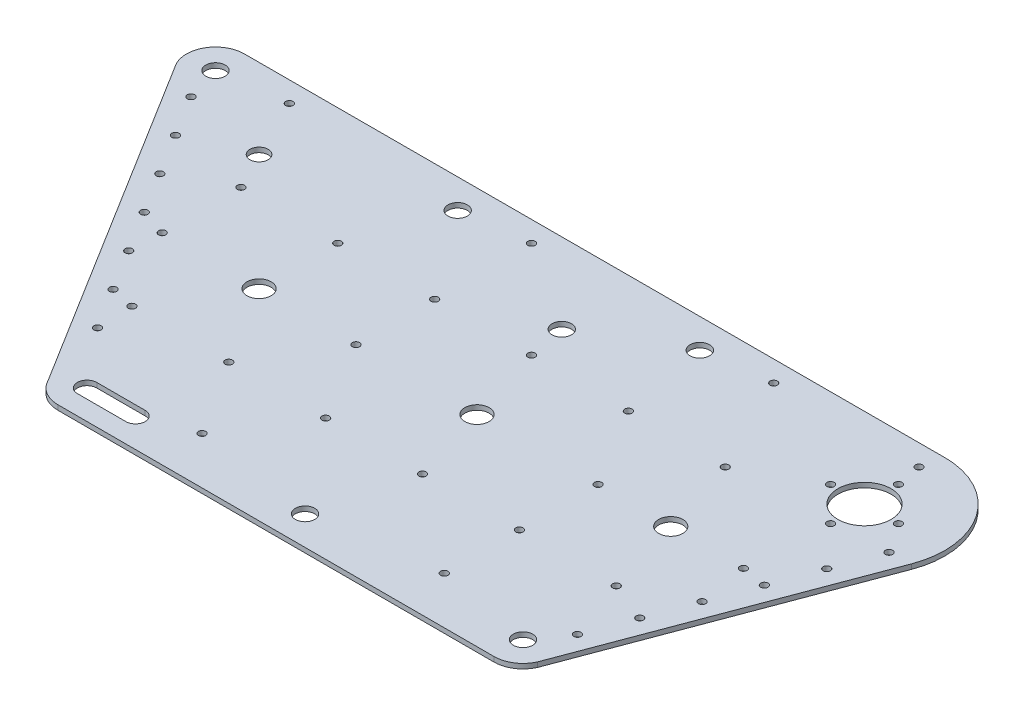
SolidWorks part; units mm, degrees
ref_plane "Front Plane" through (0, 0, 0) normal (0, 0, 1) x (1, 0, 0)
ref_plane "Top Plane" through (0, 0, 0) normal (0, 1, 0) x (1, 0, 0)
ref_plane "Right Plane" through (0, 0, 0) normal (1, 0, 0) x (0, 0, -1)
sketch "Sketch2" plane through (0, 0, 0) normal (0, 1, 0) x (1, 0, 0)
  line L0 (-106.005, 144.9436) -> (182.9628, 145.1972)
  line L1 (160.9924, -19) -> (-18.9986, -19)
  line L2 (171.9007, -12) -> (214.0696, 100.3323)
  line L3 (-18.9986, -3) -> (1.0004, -3)
  line L4 (1.0003, -11) -> (-18.9986, -11)
  line L5 (-29.6999, -12.4286) -> (-116.0853, 126.6112)
  circle A0 centre (182.992, 112) radius 11
  circle A1 centre (-18.9988, 64) radius 5
  circle A2 centre (70.9964, 64) radius 5
  circle A3 centre (150.9927, 64) radius 5
  ellipse E0 centre (-105.9945, 133) end of major axis (-105.9945, 137) minor radius 4
  ellipse E1 centre (160.9926, -7) end of major axis (160.9926, -3) minor radius 4
  ellipse E2 centre (-18.9986, -7) end of major axis (-18.9986, -11) minor radius 4 (-18.9986, -3) -> (-18.9986, -11) ccw
  ellipse E3 centre (182.992, 112) end of major axis (182.992, 123) minor radius 11
  ellipse E4 centre (-105.9945, 133) end of major axis (-105.9945, 144.9436) minor radius 11.943 (-106.005, 144.9436) -> (-116.0853, 126.6112) ccw
  ellipse E5 centre (182.992, 112) end of major axis (182.992, 145.1972) minor radius 33.1955 (214.0696, 100.3323) -> (182.9628, 145.1972) ccw
  ellipse E6 centre (1.0003, -7) end of major axis (1.0004, -3) minor radius 4 (1.0003, -11) -> (1.0004, -3) ccw
  ellipse E7 centre (182.9908, 126) end of major axis (182.9908, 127.5) minor radius 1.4999
  ellipse E8 centre (196.9901, 112) end of major axis (196.9901, 113.5) minor radius 1.4999
  ellipse E9 centre (168.9915, 112) end of major axis (168.9915, 113.5) minor radius 1.4999
  ellipse E10 centre (182.9908, 98) end of major axis (182.9908, 99.5) minor radius 1.4999
  ellipse E11 centre (-18.9986, -7) end of major axis (-18.9986, -19) minor radius 11.9993 (-29.6999, -12.4286) -> (-18.9986, -19) ccw
  ellipse E12 centre (160.9926, -7) end of major axis (160.9926, 5) minor radius 11.9994 (160.9924, -19) -> (171.9007, -12) ccw
  ellipse E13 centre (120.9939, 0.5) end of major axis (120.994, 2) minor radius 1.4999
  ellipse E14 centre (20.9989, 0.5) end of major axis (20.9989, 2) minor radius 1.4999
  ellipse E15 centre (120.9939, 64) end of major axis (120.994, 65.5) minor radius 1.4999
  ellipse E16 centre (20.9989, 64) end of major axis (20.9989, 65.5) minor radius 1.4999
  ellipse E17 centre (-58.997, 64) end of major axis (-58.997, 65.5) minor radius 1.4999
  ellipse E18 centre (180.9909, 64) end of major axis (180.9909, 65.5) minor radius 1.4999
  ellipse E19 centre (-78.996, 136.5) end of major axis (-78.996, 138) minor radius 1.4999
  ellipse E20 centre (20.9989, 136.5) end of major axis (20.9989, 138) minor radius 1.4999
  ellipse E21 centre (120.9939, 136.5) end of major axis (120.994, 138) minor radius 1.4999
  ellipse E22 centre (60.9969, 96.5) end of major axis (60.9969, 98) minor radius 1.4999
  ellipse E23 centre (140.9929, 96.5) end of major axis (140.9929, 98) minor radius 1.4999
  ellipse E24 centre (160.992, 31.5) end of major axis (160.992, 33) minor radius 1.4999
  ellipse E25 centre (80.996, 31.5) end of major axis (80.996, 33) minor radius 1.4999
  ellipse E26 centre (-18.9991, 96.5) end of major axis (-18.9991, 98) minor radius 1.4999
  ellipse E27 centre (-38.998, 31.5) end of major axis (-38.998, 33) minor radius 1.4999
  ellipse E31 centre (-101.6892, 118.5984) end of major axis (-101.6892, 120.0984) minor radius 1.4999
  ellipse E32 centre (-91.1347, 101.6106) end of major axis (-91.1347, 103.1106) minor radius 1.4999
  ellipse E33 centre (-80.5803, 84.623) end of major axis (-80.5803, 86.123) minor radius 1.4999
  ellipse E34 centre (-70.0255, 67.6347) end of major axis (-70.0255, 69.1347) minor radius 1.4999
  ellipse E35 centre (-59.4708, 50.6466) end of major axis (-59.4708, 52.1466) minor radius 1.4999
  ellipse E36 centre (-48.9163, 33.6588) end of major axis (-48.9163, 35.1588) minor radius 1.4999
  ellipse E37 centre (-38.3619, 16.6713) end of major axis (-38.3619, 18.1713) minor radius 1.4999
  ellipse E38 centre (205.3225, 99.7958) end of major axis (205.3225, 101.2958) minor radius 1.4999
  ellipse E39 centre (198.3244, 81.0602) end of major axis (198.3244, 82.5602) minor radius 1.4999
  ellipse E40 centre (191.3265, 62.3248) end of major axis (191.3265, 63.8248) minor radius 1.4999
  ellipse E41 centre (184.3286, 43.5896) end of major axis (184.3286, 45.0896) minor radius 1.4999
  ellipse E42 centre (177.3307, 24.8545) end of major axis (177.3307, 26.3545) minor radius 1.4999
  ellipse E43 centre (170.3325, 6.1186) end of major axis (170.3325, 7.6186) minor radius 1.4999
  ellipse E44 centre (180.9909, 136.5) end of major axis (180.9909, 138) minor radius 1.4999
  ellipse E45 centre (20.9989, 96.5) end of major axis (20.9989, 98) minor radius 1.4999
  ellipse E46 centre (100.995, 96.5) end of major axis (100.995, 98) minor radius 1.4999
  ellipse E47 centre (-58.9971, 96.5) end of major axis (-58.997, 98) minor radius 1.4999
  ellipse E48 centre (0.9999, 31.5) end of major axis (1, 33) minor radius 1.4999
  ellipse E49 centre (40.9979, 31.5) end of major axis (40.9979, 33) minor radius 1.4999
  ellipse E50 centre (120.9939, 31.5) end of major axis (120.994, 33) minor radius 1.4999
  ellipse E51 centre (-66.9967, 112) end of major axis (-66.9966, 115.75) minor radius 3.7498
  ellipse E52 centre (57.9973, 112) end of major axis (53.9973, 112) minor radius 4
  ellipse E53 centre (-5.9995, 133) end of major axis (-5.9995, 137) minor radius 4
  ellipse E54 centre (93.9954, 133) end of major axis (93.9954, 137) minor radius 4
  ellipse E55 centre (70.9966, -7) end of major axis (66.9966, -7) minor radius 4
  dimension "D1" = 22
  dimension "D2" = 10
  dimension "D3" = 10
  dimension "D4" = 10
extrude "Boss-Extrude1" add sketch "Sketch2" along normal blind 2 contours L1 E12 L2 E5 L0 E4 L5 E11 E55 E54 E53 E52 E51 E50 E49 E48 E47 E46 E45 E44 E43 E42 E41 E40 E39 E38 region at (58.7772, 0, -70.1515)
